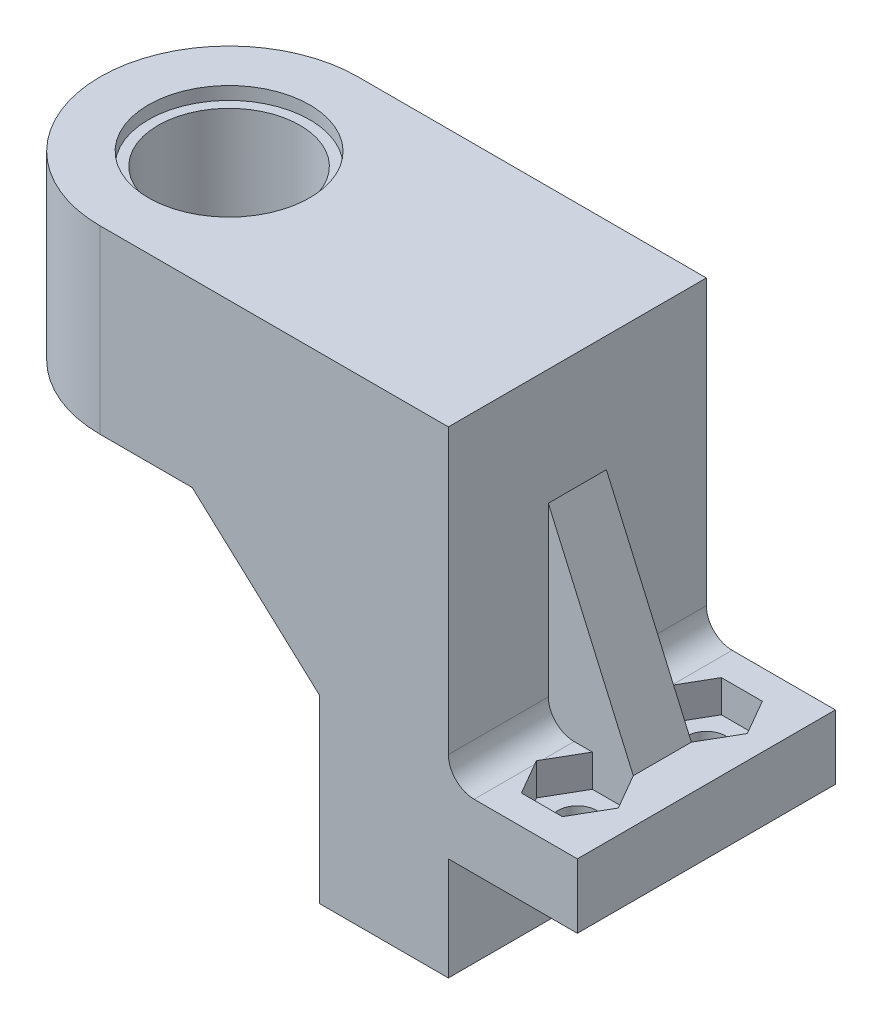
SolidWorks part; units mm, degrees
material "ABS"
ref_plane "前视基准面" through (0, 0, 0) normal (0, 0, 1) x (1, 0, 0)
ref_plane "上视基准面" through (0, 0, 0) normal (0, 1, 0) x (1, 0, 0)
ref_plane "右视基准面" through (0, 0, 0) normal (1, 0, 0) x (0, 0, -1)
sketch "草图1" plane through (0, 0, 0) normal (0, 0, 1) x (1, 0, 0)
  line L0 (-63.8668, 22.9477) -> (-23.8668, 22.9477)
  line L1 (-23.8668, 22.9477) -> (-23.8668, -19.0523)
  line L4 (-23.8668, -19.0523) -> (-33.8668, -19.0523)
  line L5 (-33.8668, -19.0523) -> (-33.8668, 14.9477)
  line L6 (-33.8668, 14.9477) -> (-63.8668, 14.9477)
  line L7 (-63.8668, 14.9477) -> (-63.8668, 22.9477)
  dimension "D2" = 42
  dimension "D3" = 10
  dimension "D5" = 8
  dimension "D6" = 30
extrude "凸台-拉伸1" add sketch "草图1" along normal blind 20
sketch "草图3" plane through (0, 22.9477, 0) normal (0, 1, 0) x (-1, 0, 0)
  line L0 (23.8668, 0) -> (63.8668, 0) construction
  line L1 (33.8668, 20) -> (33.8668, 0) construction
  circle A0 centre (50.8668, 10) radius 5.5
  dimension "D3" = 11
  dimension "D1" = 10
  dimension "D2" = 17
extrude "切除-拉伸2" cut sketch "草图3" against normal blind 10
sketch3d "3D草图2" plane through (0, 0, 0) normal (0, 0, 1) x (1, 0, 0)
sketch "草图9" plane through (0, 22.9477, 0) normal (0, 1, 0) x (1, 0, 0)
  circle A0 centre (-50.8668, -10) radius 6.25
  dimension "D1" = 12.5
extrude "切除-拉伸6" cut sketch "草图9" against normal blind 1
sketch "草图11" plane through (-23.8668, 0, 0) normal (1, 0, 0) x (0, 0, -1)
  line L0 (0, -19.0523) -> (0, 22.9477) construction
  line L1 (-20, -19.0523) -> (0, -19.0523)
  line L2 (-20, -19.0523) -> (-20, -14.0523)
  line L3 (-20, -14.0523) -> (0, -14.0523)
  line L4 (0, -19.0523) -> (0, -14.0523)
  dimension "D1" = 5
extrude "凸台-拉伸4" add sketch "草图11" along normal blind 10
sketch "草图12" plane through (0, -14.0523, 0) normal (0, 1, 0) x (-1, 0, 0)
  line L0 (13.8668, 0) -> (23.8668, 0) construction
  line L1 (13.8668, 20) -> (23.8668, 20) construction
  line L2 (13.8668, 0) -> (13.8668, 20) construction
  circle A0 centre (18.8668, 5) radius 1.5
  circle A1 centre (18.8668, 15) radius 1.5
  dimension "D1" = 3
  dimension "D4" = 5
  dimension "D5" = 5
  dimension "D2" = 5
  dimension "D3" = 5
extrude "切除-拉伸8" cut sketch "草图12" against normal up to next
sketch "草图13" plane through (0, -19.0523, 0) normal (0, -1, 0) x (1, 0, 0)
  circle A0 centre (-18.8668, 15) radius 3
  circle A1 centre (-18.8668, 5) radius 3
  dimension "D1" = 6
  dimension "D2" = 6
extrude "切除-拉伸9" cut sketch "草图13" against normal blind 2.5
sketch "草图14" plane through (0, 14.9477, 0) normal (0, -1, 0) x (1, 0, 0)
  circle A0 centre (-50.8668, 10) radius 10
  circle A1 centre (-50.8668, 10) radius 5.5
  dimension "D1" = 11
  dimension "D2" = 20
extrude "凸台-拉伸5" add sketch "草图14" along normal blind 6
sketch "草图6" plane through (0, 8.9477, 0) normal (0, -1, 0) x (1, 0, 0)
  circle A0 centre (-50.8668, 10) radius 6.25
  dimension "D1" = 12.5
extrude "切除-拉伸10" cut sketch "草图6" against normal blind 1
sketch "草图15" plane through (-13.8668, 0, 0) normal (1, 0, 0) x (0, 0, -1)
  line L1 (0, -19.0523) -> (-20, -19.0523)
  line L2 (0, -19.0523) -> (0, -14.0523)
  line L3 (0, -14.0523) -> (-20, -14.0523)
  line L4 (-20, -19.0523) -> (-20, -14.0523)
extrude "凸台-拉伸6" add sketch "草图15" along normal blind 5
sketch "草图16" plane through (0, 14.9477, 0) normal (0, -1, 0) x (1, 0, 0)
  line L1 (-33.8668, 20) -> (-50.8668, 20)
  line L2 (-33.8668, 20) -> (-33.8668, 17)
  line L3 (-33.8668, 17) -> (-50.8668, 17)
  line L4 (-50.8668, 20) -> (-50.8668, 17)
  line L5 (-33.8668, 0) -> (-50.8668, 0)
  line L6 (-33.8668, 0) -> (-33.8668, 3)
  line L7 (-33.8668, 3) -> (-50.8668, 3)
  line L8 (-50.8668, 0) -> (-50.8668, 3)
  dimension "D1" = 3
  dimension "D2" = 3
extrude "凸台-拉伸7" add sketch "草图16" along normal blind 15
sketch "草图17" plane through (0, 0, 17) normal (0, 0, -1) x (-1, 0, 0)
  line L0 (50.8668, 8.9477) -> (43.7254, 8.9477)
  line L1 (43.7254, 8.9477) -> (33.8668, -0.0523)
  line L2 (33.8668, -0.0523) -> (50.8668, -0.0523)
  line L3 (50.8668, -0.0523) -> (50.8668, 8.9477)
extrude "切除-拉伸11" cut sketch "草图17" against normal through all and the other way through all
sketch3d "3D草图3"
  line L0 (-23.8668, -14.0523, 20) -> (-23.8668, 22.9477, 20) construction
  line L1 (-23.8668, -6.0523, 20) -> (-13.8668, -6.0523, 20)
  line L2 (-23.8668, -6.0523, 20) -> (-23.8668, -6.0523, 0)
  line L3 (-23.8668, -6.0523, 0) -> (-13.8668, -6.0523, 0)
  line L4 (-13.8668, -6.0523, 20) -> (-13.8668, -6.0523, 0)
  circle A0 centre (-18.8668, -6.0523, 15) radius 1.5
  circle A1 centre (-18.8668, -6.0523, 5) radius 1.5
  point P8 (-18.8668, -4.5523, 15)
  point P11 (-18.8668, -4.5523, 5)
  dimension "D4" = 3
  dimension "D5" = 3
  dimension "D6" = 5
  dimension "D7" = 5
  dimension "D8" = 5
  dimension "D9" = 5
  dimension "D1" = 8
  dimension "D2" = 10
  dimension "D3" = 20
extrude "凸台-拉伸8" add sketch "3D草图3" along a picked direction on the side against the normal blind 5
sketch "草图18" plane through (0, -1.0523, 0) normal (0, 1, 0) x (-1, 0, 0)
  line L1 (15.6914, 15) -> (17.2791, 12.25)
  line L2 (17.2791, 12.25) -> (20.4545, 12.25)
  line L3 (20.4545, 12.25) -> (22.0422, 15)
  line L4 (22.0422, 15) -> (20.4545, 17.75)
  line L5 (20.4545, 17.75) -> (17.2791, 17.75)
  line L6 (17.2791, 17.75) -> (15.6914, 15)
  line L7 (15.6914, 5) -> (17.2791, 2.25)
  line L8 (17.2791, 2.25) -> (20.4545, 2.25)
  line L9 (20.4545, 2.25) -> (22.0422, 5)
  line L10 (22.0422, 5) -> (20.4545, 7.75)
  line L11 (20.4545, 7.75) -> (17.2791, 7.75)
  line L12 (17.2791, 7.75) -> (15.6914, 5)
  circle A0 centre (18.8668, 15) radius 2.75 construction
  circle A1 centre (18.8668, 5) radius 2.75 construction
  dimension "D1" = 5.5
  dimension "D2" = 5.5
extrude "切除-拉伸12" cut sketch "草图18" against normal blind 2.5
fillet "圆角1" radius 2 1 edges
sketch "草图19" plane through (0, 22.9477, 0) normal (0, 1, 0) x (1, 0, 0)
  line L0 (-23.8668, -17) -> (-31.8668, -17)
  line L1 (-23.8668, -20) -> (-23.8668, 0) construction
  line L2 (-31.8668, -17) -> (-31.8668, -20)
  line L3 (-23.8668, -20) -> (-63.8668, -20) construction
  line L4 (-31.8668, -20) -> (-23.8668, -20)
  line L5 (-23.8668, -20) -> (-23.8668, -17)
  dimension "D1" = 8
  dimension "D2" = 3
extrude "切除-拉伸13" [suppressed] cut sketch "草图19" against normal blind 13
sketch "草图20" plane through (0, 14.9477, 0) normal (0, -1, 0) x (1, 0, 0)
  line L0 (-63.8668, 20) -> (-50.8668, 20)
  line L2 (-50.8668, 0) -> (-63.8668, 0)
  line L3 (-63.8668, 0) -> (-63.8668, 20)
  arc A0 (-50.8668, 20) -> (-50.8668, 0) centre (-50.8668, 10) ccw
extrude "切除-拉伸14" cut sketch "草图20" against normal through all
sketch "草图21" plane through (0, -1.0523, 0) normal (0, 1, 0) x (1, 0, 0)
  line L0 (-17.2791, -7.75) -> (-23.8668, -7.75)
  line L1 (-23.8668, -20) -> (-23.8668, 0) construction
  line L2 (-23.8668, -7.75) -> (-23.8668, -12.25)
  line L3 (-23.8668, -12.25) -> (-17.2791, -12.25)
  line L4 (-17.2791, -12.25) -> (-17.2791, -7.75)
extrude "凸台-拉伸9" add sketch "草图21" along normal blind 15
sketch "草图22" [suppressed] plane through (0, 0, 12.25) normal (0, 0, 1) x (1, 0, 0)
  line L0 (-17.2791, 13.9477) -> (-23.8668, 13.9477)
  line L1 (-23.8668, 9.9477) -> (-23.8668, 22.9477) construction
  line L2 (-23.8668, 13.9477) -> (-17.2791, -1.0523)
  line L3 (-17.2791, -1.0523) -> (-17.2791, 13.9477)
extrude "切除-拉伸15" [suppressed] cut sketch "草图22" against normal up to next
fillet "圆角3" [suppressed] radius 2
sketch "草图23" plane through (0, -19.0523, 0) normal (0, -1, 0) x (1, 0, 0)
  line L1 (-33.8668, 0) -> (-8.8668, 0)
  line L2 (-33.8668, 0) -> (-33.8668, 20)
  line L3 (-33.8668, 20) -> (-8.8668, 20)
  line L4 (-8.8668, 0) -> (-8.8668, 20)
extrude "切除-拉伸16" cut sketch "草图23" against normal up to surface (5 mm away) up to face at (-20.3668, -14.0523, 15)
sketch "草图24" plane through (0, 0, 12.25) normal (0, 0, 1) x (1, 0, 0)
  line L0 (-23.8668, 13.9477) -> (-17.2791, -1.0523)
  line L1 (-17.2791, -1.0523) -> (-17.2791, 13.9477)
  line L2 (-17.2791, 13.9477) -> (-23.8668, 13.9477)
extrude "切除-拉伸17" cut sketch "草图24" against normal blind 10
